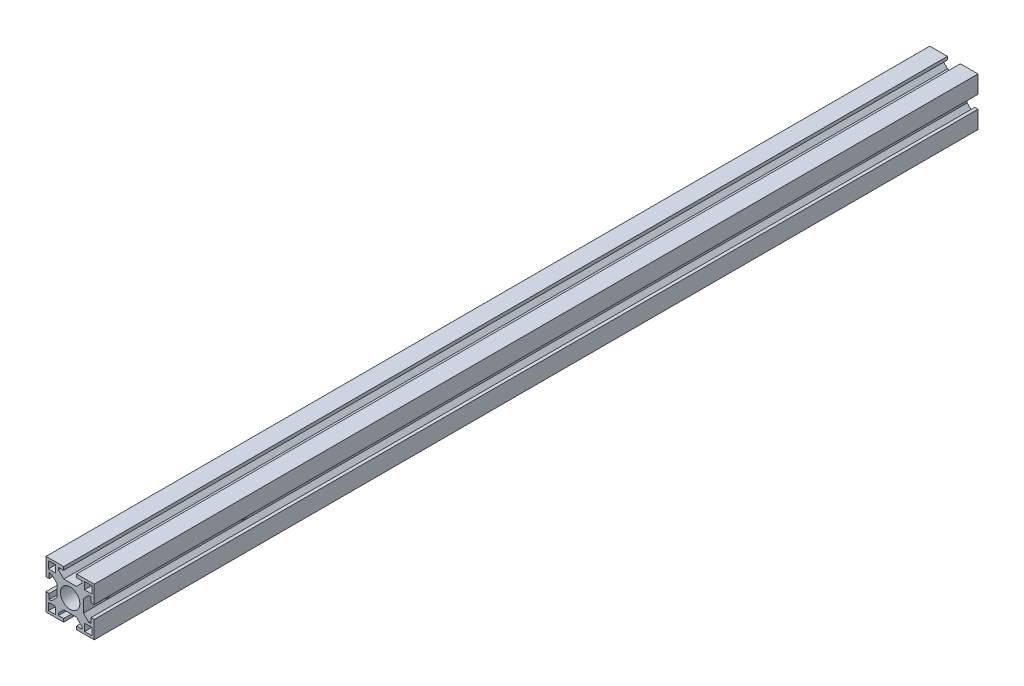
SolidWorks part; units mm, degrees
ref_plane "Ebene vorne" through (0, 0, 0) normal (0, 0, 1) x (1, 0, 0)
ref_plane "Ebene oben" through (0, 0, 0) normal (0, 1, 0) x (1, 0, 0)
ref_plane "Ebene rechts" through (0, 0, 0) normal (1, 0, 0) x (0, 0, -1)
ref_plane "Ebene1" through (0, 0, 0) normal (0, 0, -1) x (-1, 0, 0)
sketch "Skizze1" plane through (0, 0, 0) normal (0, 0, -1) x (-1, 0, 0)
  line L0 (15, -15) -> (15, -4)
  line L1 (15, -4) -> (13, -4)
  line L2 (13, -4) -> (13, -7.2657)
  line L3 (13, -7.2657) -> (11.6343, -7.2657)
  line L4 (11.6343, -7.2657) -> (8.3, -3.9314)
  line L5 (8.3, -3.9314) -> (8.3, 3.9314)
  line L6 (8.3, 3.9314) -> (11.6343, 7.2657)
  line L7 (11.6343, 7.2657) -> (13, 7.2657)
  line L8 (13, 7.2657) -> (13, 4)
  line L9 (13, 4) -> (15, 4)
  line L10 (15, 4) -> (15, 15)
  line L11 (15, 15) -> (4, 15)
  line L12 (4, 15) -> (4, 13)
  line L13 (4, 13) -> (7.2657, 13)
  line L14 (7.2657, 13) -> (7.2657, 11.6343)
  line L15 (7.2657, 11.6343) -> (3.9314, 8.3)
  line L16 (3.9314, 8.3) -> (-3.9314, 8.3)
  line L17 (-3.9314, 8.3) -> (-7.2657, 11.6343)
  line L18 (-7.2657, 11.6343) -> (-7.2657, 13)
  line L19 (-7.2657, 13) -> (-4, 13)
  line L20 (-4, 13) -> (-4, 15)
  line L21 (-4, 15) -> (-15, 15)
  line L22 (-15, 15) -> (-15, 4)
  line L23 (-15, 4) -> (-13, 4)
  line L24 (-13, 4) -> (-13, 7.2657)
  line L25 (-13, 7.2657) -> (-11.6343, 7.2657)
  line L26 (-11.6343, 7.2657) -> (-8.3, 3.9314)
  line L27 (-8.3, 3.9314) -> (-8.3, -3.9314)
  line L28 (-8.3, -3.9314) -> (-11.6343, -7.2657)
  line L29 (-11.6343, -7.2657) -> (-13, -7.2657)
  line L30 (-13, -7.2657) -> (-13, -4)
  line L31 (-13, -4) -> (-15, -4)
  line L32 (-15, -4) -> (-15, -15)
  line L33 (-15, -15) -> (-4, -15)
  line L34 (-4, -15) -> (-4, -13)
  line L35 (-4, -13) -> (-7.2657, -13)
  line L36 (-7.2657, -13) -> (-7.2657, -11.6343)
  line L37 (-7.2657, -11.6343) -> (-3.9314, -8.3)
  line L38 (-3.9314, -8.3) -> (3.9314, -8.3)
  line L39 (3.9314, -8.3) -> (7.2657, -11.6343)
  line L40 (7.2657, -11.6343) -> (7.2657, -13)
  line L41 (7.2657, -13) -> (4, -13)
  line L42 (4, -13) -> (4, -15)
  line L43 (4, -15) -> (15, -15)
  line L44 (9, 13.5) -> (13.5, 13.5)
  line L45 (13.5, 13.5) -> (13.5, 9)
  line L46 (13.5, 9) -> (9, 9)
  line L47 (9, 9) -> (9, 13.5)
  line L48 (13.5, -9) -> (13.5, -13.5)
  line L49 (13.5, -13.5) -> (9, -13.5)
  line L50 (9, -13.5) -> (9, -9)
  line L51 (9, -9) -> (13.5, -9)
  line L52 (-9, -13.5) -> (-13.5, -13.5)
  line L53 (-13.5, -13.5) -> (-13.5, -9)
  line L54 (-13.5, -9) -> (-9, -9)
  line L55 (-9, -9) -> (-9, -13.5)
  line L56 (-13.5, 9) -> (-13.5, 13.5)
  line L57 (-13.5, 13.5) -> (-9, 13.5)
  line L58 (-9, 13.5) -> (-9, 9)
  line L59 (-9, 9) -> (-13.5, 9)
  circle A0 centre (0, 0) radius 6.05
extrude "Aufsatz-Linear austragen1" add sketch "Skizze1" against normal blind 550
sketch "Skizze3" plane through (-15, 0, 0) normal (-1, 0, 0) x (0, 0, 1)
  line L0 (550, -15) -> (550, -4) construction
  circle A0 centre (535, 0) radius 3.3
  circle A1 centre (450, 0) radius 3.3
  dimension "D1" = 85
  dimension "D2" = 15
  dimension "D3" = 6.6
extrude "Schnitt-Linear austragen2" cut sketch "Skizze3" against normal through all
